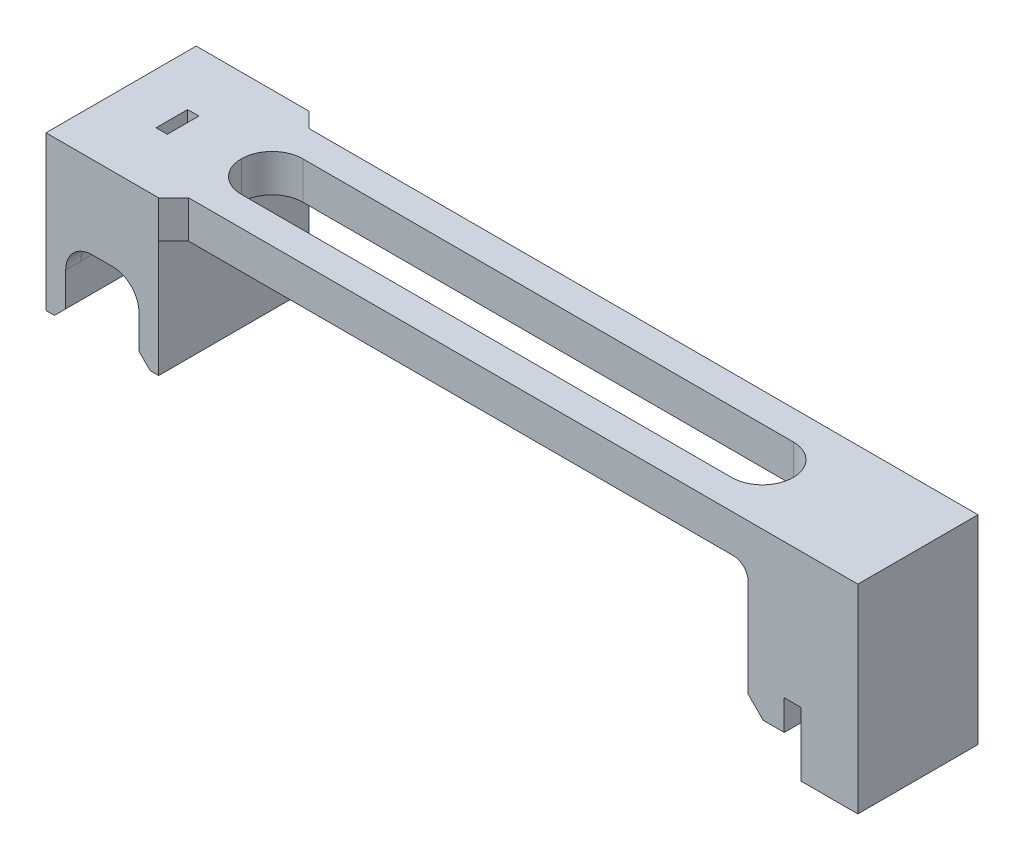
SolidWorks part; units mm, degrees
ref_plane "정면" through (0, 0, 0) normal (0, 0, 1) x (1, 0, 0)
ref_plane "윗면" through (0, 0, 0) normal (0, 1, 0) x (1, 0, 0)
ref_plane "우측면" through (0, 0, 0) normal (1, 0, 0) x (0, 0, -1)
sketch "스케치1" plane through (0, 0, 0) normal (0, 0, 1) x (1, 0, 0)
  line L0 (-96, 0) -> (0, 0)
  line L1 (0, 0) -> (0, -21.5)
  line L2 (0, -21.5) -> (7.6, -21.5)
  line L3 (7.6, -21.5) -> (7.6, 5)
  line L4 (7.6, 5) -> (-96, 5)
  line L5 (-96, 5) -> (-96, 0)
  dimension "D1" = 5
  dimension "D2" = 96
  dimension "D3" = 7.6
  dimension "D4" = 21.5
extrude "보스-돌출1" add sketch "스케치1" along normal blind 16
sketch "스케치4" plane through (0, 0, 0) normal (0, -1, 0) x (1, 0, 0)
  line L0 (-96, 8) -> (-7.1358, 8) construction
  line L1 (-96, 16) -> (-96, 0) construction
  line L2 (0, 16) -> (0, 0) construction
  line L3 (-91.75, 5.9) -> (-90.25, 5.9)
  line L4 (-91.75, 5.9) -> (-91.75, 10.1)
  line L5 (-91.75, 10.1) -> (-90.25, 10.1)
  line L6 (-90.25, 5.9) -> (-90.25, 10.1)
  line L7 (-91.75, 5.9) -> (-90.25, 10.1) construction
  line L8 (-91.75, 10.1) -> (-90.25, 5.9) construction
  line L9 (-9, 3.9) -> (-82.5, 3.9)
  line L10 (-9, 3.9) -> (-9, 12.1)
  line L11 (-9, 12.1) -> (-82.5, 12.1)
  line L12 (-82.5, 3.9) -> (-82.5, 12.1)
  line L13 (-9, 3.9) -> (-82.5, 12.1) construction
  line L14 (-9, 12.1) -> (-82.5, 3.9) construction
  point P4 (-91, 8)
  point P9 (-45.75, 8)
  dimension "D1" = 1.5
  dimension "D2" = 4.25
  dimension "D3" = 7.75
  dimension "D4" = 9
  dimension "D5" = 8.2
  dimension "D6" = 4.2
extrude "컷-돌출1" cut sketch "스케치4" against normal blind 10
fillet "필렛1" radius 4.1 4 edges at (-82.5, 2.5, 3.9) (-82.5, 2.5, 12.1) (-9, 2.5, 3.9) (-9, 2.5, 12.1)
sketch "스케치6" plane through (0, 5, 0) normal (0, 1, 0) x (1, 0, 0)
  line L0 (7.6, -16) -> (-96, -16) construction
  line L1 (-96, 0) -> (-86, 0)
  line L2 (-96, 0) -> (-96, -16)
  line L3 (-96, -16) -> (-86, -16)
  line L4 (-86, 0) -> (-86, -16)
  line L6 (-90.25, -5.9) -> (-90.25, -10.1) construction
  line M5 (-91.75, -5.9) -> (-90.25, -5.9)
  line M6 (-90.25, -5.9) -> (-90.25, -10.1)
  line M7 (-90.25, -10.1) -> (-91.75, -10.1)
  line M8 (-91.75, -10.1) -> (-91.75, -5.9)
  line M15 (7.6, 0) -> (-96, 0)
  line M16 (-96, 0) -> (-96, -16)
  line M17 (-96, -16) -> (7.6, -16)
  dimension "D1" = 4.25
extrude "보스-돌출4" add sketch "스케치6" against normal blind 11 contours L4 M15 M16 M17 M8 M5 M6 M7 region at (-91, 5, 0.1887)
sketch "스케치10" plane through (0, -6, 0) normal (0, -1, 0) x (1, 0, 0)
  line L0 (-91, 10.1) -> (-91, 5.9) construction
  line L1 (-90.25, 10.1) -> (-91.75, 10.1) construction
  line L2 (-91.75, 5.9) -> (-90.25, 5.9) construction
  line L3 (-91.75, 8) -> (-90.25, 8) construction
  line L4 (-91.75, 10.1) -> (-91.75, 5.9) construction
  line L5 (-90.25, 5.9) -> (-90.25, 10.1) construction
  line L7 (-95.875, 0) -> (-86.125, 0)
  line L8 (-95.875, 0) -> (-95.875, 16)
  line L9 (-95.875, 16) -> (-86.125, 16)
  line L10 (-86.125, 0) -> (-86.125, 16)
  line L11 (-95.875, 0) -> (-86.125, 16) construction
  line L12 (-95.875, 16) -> (-86.125, 0) construction
  line L13 (-98.5, 0) -> (-83.5, 0)
  line L14 (-98.5, 0) -> (-98.5, 16)
  line L15 (-98.5, 16) -> (-83.5, 16)
  line L16 (-83.5, 0) -> (-83.5, 16)
  line L17 (-98.5, 0) -> (-83.5, 16) construction
  line L18 (-98.5, 16) -> (-83.5, 0) construction
  point P12 (-91, 8)
  point P17 (-91, 8)
  line M6 (-86, 0) -> (-86, 16)
  line M7 (-86, 16) -> (-96, 16)
  line M8 (-96, 16) -> (-96, 0)
  line M9 (-96, 0) -> (-86, 0)
  dimension "D1" = 9.75
  dimension "D2" = 15
extrude "보스-돌출6" add sketch "스케치10" along normal blind 13 and the other way up to vertex (11 mm away) contours L8 M9 M7 M8 | L15 L14 L13 M8 | L10 M9 M6 M7 | L13 L16 L15 M6 region at (-95.9375, -6, 8) region at (-86.0625, -6, 8) region at (-97.25, -6, 8) region at (-84.75, -6, 8) other way up to point (7.6, 5, 16)
fillet "필렛2" radius 3.5 2 edges at (-86.125, -6, 8) (-95.875, -6, 8)
sketch "스케치11" plane through (0, 0, 16) normal (0, 0, 1) x (1, 0, 0)
  line L0 (-98.5, 5) -> (-98.5, -19)
  line L1 (-98.5, -19) -> (-95.875, -19)
  line L2 (-92.375, -6) -> (-83.5, -6) construction
  line L3 (-83.5, -19) -> (-83.5, 0) construction
  line L4 (-83.5, -6) -> (-98.5, -6) construction
  line L5 (-95.875, -19) -> (-95.875, -6)
  line L6 (-86.125, -19) -> (-86.125, -6)
  line L7 (-86.125, -6) -> (-95.875, -6)
  line L8 (-86.125, -19) -> (-83.5, -19)
  line L9 (-83.5, -19) -> (-83.5, 5)
  line L10 (7.6, 5) -> (-98.5, 5) construction
  line L11 (-83.5, 5) -> (-98.5, 5)
extrude "보스-돌출7" add sketch "스케치11" along normal blind 2
sketch "스케치12" plane through (0, 0, 0) normal (0, 0, -1) x (-1, 0, 0)
  line L0 (89.625, -6) -> (98.5, -6) construction
  line L1 (98.5, 5) -> (98.5, -19) construction
  line L2 (98.5, -6) -> (83.5, -6) construction
  line L3 (83.5, -19) -> (83.5, 0) construction
  line L4 (83.5, 5) -> (83.5, -19)
  line L5 (-7.6, 5) -> (98.5, 5) construction
  line L6 (83.5, -19) -> (86.125, -19)
  line L7 (86.125, -19) -> (86.125, -6)
  line L8 (83.5, 5) -> (98.5, 5)
  line L9 (98.5, 5) -> (98.5, -19)
  line L10 (98.5, -19) -> (95.875, -19)
  line L11 (95.875, -19) -> (95.875, -6)
  line L12 (95.875, -6) -> (86.125, -6)
extrude "보스-돌출8" add sketch "스케치12" along normal blind 2
fillet "필렛4" radius 3.5 4 edges at (-95.875, -6, -1) (-86.125, -6, -1) (-86.125, -6, 17) (-95.875, -6, 17)
sketch "스케치13" plane through (-98.5, 0, 0) normal (-1, 0, 0) x (0, 0, 1)
  line L0 (18, 5) -> (18, -19) construction
  line L1 (-2, -19) -> (18, -19)
  line L2 (-2, -19) -> (-2, -15.5)
  line L3 (-2, -15.5) -> (18, -15.5)
  line L4 (18, -19) -> (18, -15.5)
  dimension "D1" = 3.5
extrude "컷-돌출2" cut sketch "스케치13" against normal up to vertex (15 mm away) up to point (-83.5, -19, -2)
chamfer "모따기1" distance 2 2 edges at (-83.5, 2.5, 16) (-83.5, 2.5, 0)
chamfer "모따기2" distance 1.5 angle 45 2 edges at (-95.875, -15.5, 8) (-86.125, -15.5, 8)
sketch "스케치14" plane through (0, 0, 0) normal (0, -1, 0) x (1, 0, 0)
  line L1 (-81.5, 0) -> (0, 0) construction
  line L2 (0, 16) -> (-7, 16)
  line L3 (0, 16) -> (0, 0)
  line L4 (0, 0) -> (-7, 0)
  line L5 (-7, 16) -> (-7, 0)
  dimension "D1" = 7
extrude "보스-돌출9" add sketch "스케치14" along normal blind 13
sketch "스케치15" plane through (0, -13, 0) normal (0, -1, 0) x (1, 0, 0)
  line L7 (-7, 0) -> (0, 0) construction
  line L8 (-7, 16) -> (-2.2, 16)
  line L9 (-7, 16) -> (-7, 0)
  line L10 (-7, 0) -> (-2.2, 0)
  line L11 (-2.2, 16) -> (-2.2, 0)
  line L12 (0, 0) -> (0, 16) construction
  dimension "D1" = 2.2
extrude "보스-돌출10" add sketch "스케치15" along normal blind 4
fillet "필렛5" radius 2 1 edges at (-7, 0, 8)
chamfer "모따기3" distance 2 1 edges at (-7, -17, 8)
